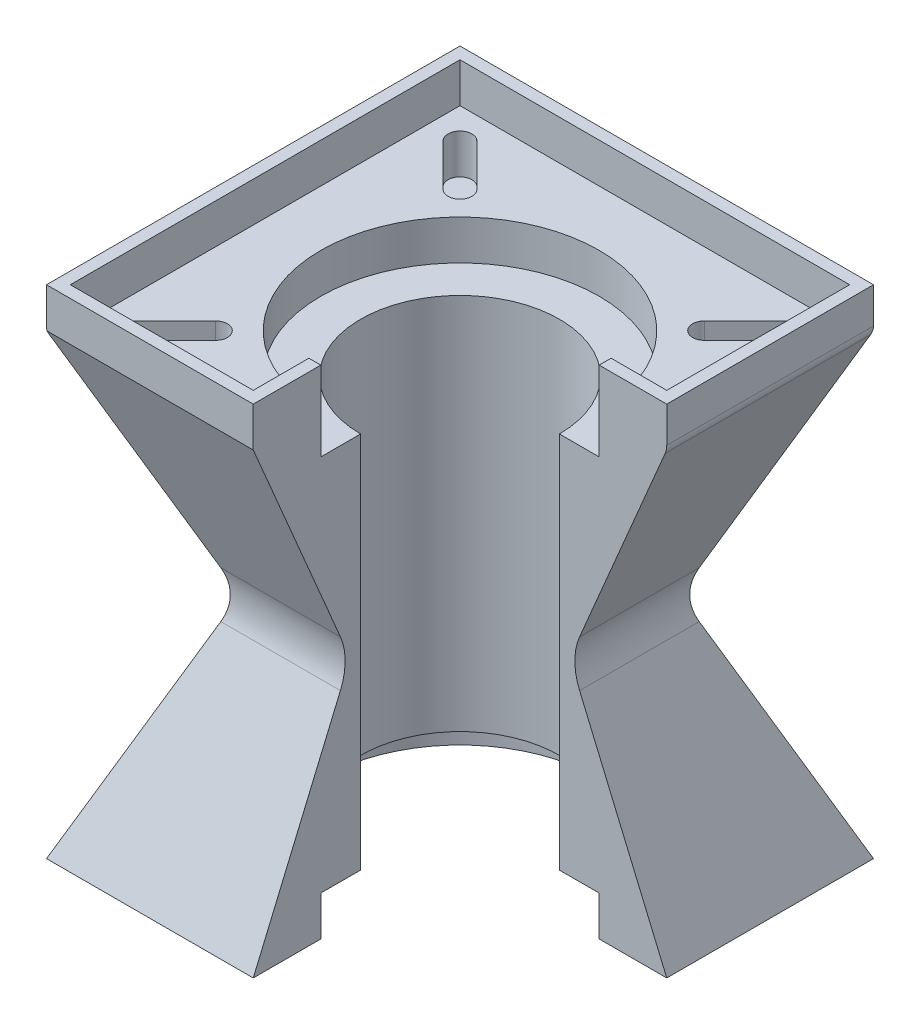
SolidWorks part; units mm, degrees
material "Cast Stainless Steel"
ref_plane "Front Plane" through (0, 0, 0) normal (0, 0, 1) x (1, 0, 0)
ref_plane "Top Plane" through (0, 0, 0) normal (0, 1, 0) x (1, 0, 0)
ref_plane "Right Plane" through (0, 0, 0) normal (1, 0, 0) x (0, 0, -1)
sketch "Sketch1" plane through (0, 0, 0) normal (0, 1, 0) x (1, 0, 0)
  line L1 (0, 0) -> (104, 0)
  line L2 (0, 0) -> (0, 104)
  line L3 (0, 104) -> (104, 104)
  line L4 (104, 0) -> (104, 104)
  dimension "D1" = 104
  dimension "D2" = 104
extrude "Boss-Extrude1" add sketch "Sketch1" along normal blind 57.5 draft 23
mirror "Mirror1" about plane through (0, 57.5, 0) normal (0, -1, 0) of bodies 101
sketch "Sketch2" plane through (0, 115, 0) normal (0, 1, 0) x (1, 0, 0)
  line L0 (104, 104) -> (0, 104) construction
  line L1 (104, 0) -> (104, 104) construction
  circle A0 centre (52, 52) radius 25
  dimension "D1" = 50
  dimension "D2" = 52
  dimension "D3" = 52
extrude "Cut-Extrude1" cut sketch "Sketch2" against normal through all
fillet "Fillet1" radius 15 4 edges at (52, 57.5, -24.4073) (24.4073, 57.5, -52) (52, 57.5, -79.5927) (79.5927, 57.5, -52)
sketch "Sketch3" plane through (0, 115, 0) normal (0, 1, 0) x (1, 0, 0)
  circle A0 centre (52, 52) radius 35
  point P3 (0, 0)
  dimension "D1" = 70
extrude "Cut-Extrude2" cut sketch "Sketch3" against normal blind 10
sketch "Sketch5" plane through (0, 0, 0) normal (0, -1, 0) x (1, 0, 0)
  line L0 (0, 0) -> (104, 0) construction
  line L1 (104, 0) -> (104, -104) construction
  circle A0 centre (52, -52) radius 35
  dimension "D2" = 52
  dimension "D3" = 52
  dimension "D1" = 70
extrude "Cut-Extrude3" cut sketch "Sketch5" against normal blind 10
sketch "Sketch6" plane through (0, 115, 0) normal (0, 1, 0) x (1, 0, 0)
  line L1 (52, 52) -> (104, 52)
  line L2 (52, 52) -> (52, 0)
  line L3 (52, 0) -> (104, 0)
  line L4 (104, 52) -> (104, 0)
extrude "Cut-Extrude4" cut sketch "Sketch6" against normal through all
sketch "Sketch7" plane through (0, 115, 0) normal (0, 1, 0) x (1, 0, 0)
  line L0 (52, 17) -> (52, 0) construction
  line L1 (0, 0) -> (52, 0) construction
  line L2 (0, 104) -> (0, 0) construction
  line L3 (104, 52) -> (104, 104) construction
  line L4 (104, 104) -> (0, 104) construction
  line L5 (52, 17) -> (52, 0)
  line L6 (0, 0) -> (52, 0)
  line L7 (0, 104) -> (0, 0)
  line L8 (104, 52) -> (104, 104)
  line L9 (104, 104) -> (0, 104)
  line L10 (101, 55) -> (101, 101)
  line L11 (101, 101) -> (3, 101)
  line L12 (3, 101) -> (3, 3)
  line L13 (3, 3) -> (49, 3)
  line L14 (49, 17) -> (49, 3)
  line L15 (104, 52) -> (87, 52) construction
  line L16 (104, 52) -> (87, 52)
  line L17 (101, 55) -> (87, 55)
  line L18 (104, 55) -> (87, 55) construction
  line L19 (101, 52) -> (101, 101) construction
  line L20 (87, 55) -> (87, 52)
  line L21 (49, 17) -> (52, 17)
  dimension "D1" = 3
  dimension "D2" = 3
extrude "Boss-Extrude2" add sketch "Sketch7" along normal blind 10
fillet "Fillet2" radius 5 4 edges at (26, 115, -3) (0, 115, -52) (52, 115, -104) (104, 115, -78)
sketch "Sketch8" plane through (0, 115, 0) normal (0, 1, 0) x (1, 0, 0)
  line L0 (52, 52) -> (0, 104) construction
  line L1 (0, 0) -> (104, 104) construction
  line L2 (52, 52) -> (52, 104) construction
  line L3 (104, 104) -> (0, 104) construction
  line L4 (52, 52) -> (0, 52) construction
  line L5 (0, 104) -> (0, 0) construction
  line L6 (10.6387, 93.3613) -> (21.2453, 82.7547) construction
  line L7 (12.76, 95.4826) -> (23.3666, 84.876)
  line L8 (8.5174, 91.24) -> (19.124, 80.6334)
  line L9 (10.6387, 10.6387) -> (21.2453, 21.2453) construction
  line L10 (12.76, 8.5174) -> (23.3666, 19.124)
  line L11 (8.5174, 12.76) -> (19.124, 23.3666)
  line L12 (93.3613, 93.3613) -> (82.7547, 82.7547) construction
  line L13 (91.24, 95.4826) -> (80.6334, 84.876)
  line L14 (95.4826, 91.24) -> (84.876, 80.6334)
  circle A0 centre (52, 52) radius 50 construction
  arc A1 (12.76, 95.4826) -> (8.5174, 91.24) centre (10.6387, 93.3613) ccw
  arc A2 (19.124, 80.6334) -> (23.3666, 84.876) centre (21.2453, 82.7547) ccw
  arc A3 (12.76, 8.5174) -> (8.5174, 12.76) centre (10.6387, 10.6387) cw
  arc A4 (19.124, 23.3666) -> (23.3666, 19.124) centre (21.2453, 21.2453) cw
  arc A5 (91.24, 95.4826) -> (95.4826, 91.24) centre (93.3613, 93.3613) cw
  arc A6 (84.876, 80.6334) -> (80.6334, 84.876) centre (82.7547, 82.7547) cw
  point P17 (15.942, 88.058)
  point P22 (0, 0)
  point P23 (0, 0)
  point P24 (0, 0)
  point P25 (0, 0)
  point P28 (15.942, 15.942)
  point P35 (88.058, 88.058)
  dimension "D1" = 100
  dimension "D3" = 3
  dimension "D2" = 15
extrude "Cut-Extrude5" cut sketch "Sketch8" against normal blind 10
equation "\"A\"= 115mm"
equation "\"B\"= 104mm"
equation "\"C\" = 23deg"
equation "\"D1@Sketch1\"=\"B\""
equation "\"D2@Sketch1\"=\"B\""
equation "\"D1@Boss-Extrude1\"=\"A\"/2"
equation "\"D3@Boss-Extrude1\"=\"C\""
equation "\"D2@Sketch2\"=\"B\"/2"
equation "\"D3@Sketch2\"=\"B\"/2"
equation "\"D2@Sketch5\"=\"B\"/2"
equation "\"D3@Sketch5\"=\"B\"/2"
